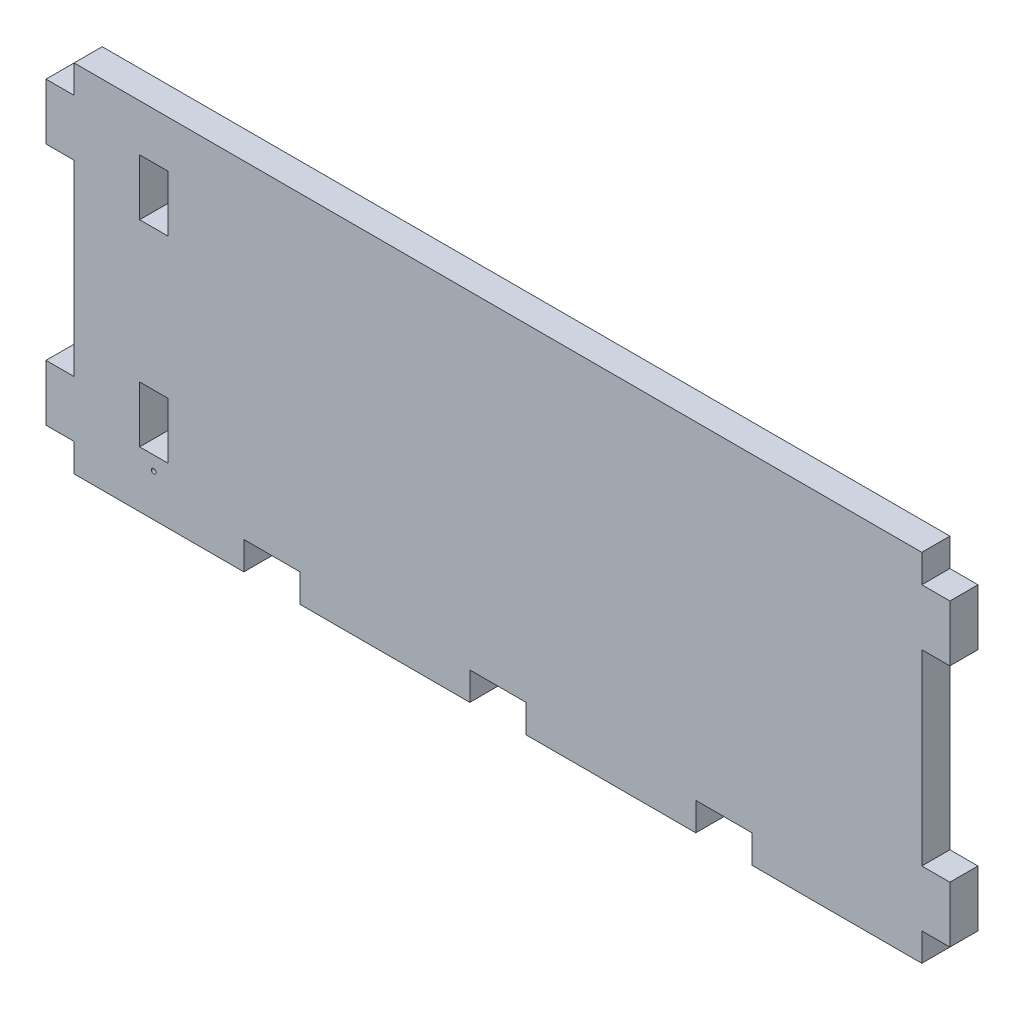
SolidWorks part; units mm, degrees
ref_plane "Front Plane" through (0, 0, 0) normal (0, 0, 1) x (1, 0, 0)
ref_plane "Top Plane" through (0, 0, 0) normal (0, 1, 0) x (1, 0, 0)
ref_plane "Right Plane" through (0, 0, 0) normal (1, 0, 0) x (0, 0, -1)
sketch "Sketch2" plane through (0, 0, 0) normal (0, 1, 0) x (1, 0, 0)
  line L0 (0, 0) -> (0, 6) construction
  dimension "D1" = 6
sketch "Sketch1" plane through (0, 0, 0) normal (0, 0, 1) x (1, 0, 0)
  line L0 (-90.5, 32) -> (-90.5, 38)
  line L1 (-96.5, -38) -> (96.5, -38)
  line L2 (-96.5, -38) -> (-96.5, 38)
  line L3 (-96.5, 38) -> (96.5, 38)
  line L4 (96.5, -38) -> (96.5, 38)
  line L5 (-96.5, -38) -> (96.5, 38) construction
  line L6 (-96.5, 38) -> (96.5, -38) construction
  line L7 (-96.5, -32) -> (-90.5, -32)
  line L8 (-96.5, -32) -> (-96.5, -20)
  line L9 (-96.5, -20) -> (-90.5, -20)
  line L10 (-90.5, -32) -> (-90.5, -20)
  line L11 (-96.5, 32) -> (-90.5, 32)
  line L12 (-96.5, 32) -> (-96.5, 20)
  line L13 (-96.5, 20) -> (-90.5, 20)
  line L14 (-90.5, 32) -> (-90.5, 20)
  line L15 (96.5, 32) -> (90.5, 32)
  line L16 (96.5, 32) -> (96.5, 20)
  line L17 (96.5, 20) -> (90.5, 20)
  line L18 (90.5, 32) -> (90.5, 20)
  line L19 (90.5, -20) -> (96.5, -20)
  line L20 (90.5, -20) -> (90.5, -32)
  line L21 (90.5, -32) -> (96.5, -32)
  line L22 (96.5, -20) -> (96.5, -32)
  line L23 (-90.5, -32) -> (-90.5, -38)
  line L24 (-90.5, 20) -> (-90.5, -20)
  line L25 (90.5, 32) -> (90.5, 38)
  line L26 (90.5, 20) -> (90.5, -20)
  line L27 (90.5, -32) -> (90.5, -38)
  line L28 (-90.5, 0) -> (-76.5, 0) construction
  line L29 (54.25, -32) -> (90.5, -32) construction
  line L30 (-76.5, 0) -> (-76.5, 16) construction
  line L31 (-76.5, 16) -> (-76.5, 28)
  line L32 (-76.5, 28) -> (-76.5, 38) construction
  line L33 (-76.5, 28) -> (-70.5, 28)
  line L34 (-70.5, 28) -> (-70.5, 16)
  line L35 (-70.5, 16) -> (-76.5, 16)
  line L36 (-76.5, -26) -> (-76.5, -14)
  line L37 (-76.5, -14) -> (-70.5, -14)
  line L38 (-70.5, -14) -> (-70.5, -26)
  line L39 (-70.5, -26) -> (-76.5, -26)
  line L40 (-76.5, -32) -> (-76.5, -26) construction
  line L41 (-76.5, -14) -> (-76.5, 0) construction
  line L42 (-90.5, -32) -> (-54.25, -32) construction
  line L43 (6, -38) -> (-6, -38)
  line L44 (6, -38) -> (6, -32)
  line L45 (6, -32) -> (-6, -32)
  line L46 (-6, -38) -> (-6, -32)
  line L47 (42.25, -38) -> (54.25, -38)
  line L48 (42.25, -38) -> (42.25, -32)
  line L49 (42.25, -32) -> (54.25, -32)
  line L50 (54.25, -38) -> (54.25, -32)
  line L51 (-42.25, -38) -> (-54.25, -38)
  line L52 (-42.25, -38) -> (-42.25, -32)
  line L53 (-42.25, -32) -> (-54.25, -32)
  line L54 (-54.25, -38) -> (-54.25, -32)
  line L55 (-42.25, -32) -> (-6, -32) construction
  line L56 (6, -32) -> (42.25, -32) construction
  point P0 (0, 0)
  dimension "D1" = 193
  dimension "D2" = 76
  dimension "D3" = 6
  dimension "D4" = 12
  dimension "D5" = 14
  dimension "D6" = 10
extrude "Boss-Extrude1" add sketch "Sketch1" against normal up to vertex (6 mm away) contours L1 L54 L53 L52 L46 L45 L44 L48 L49 L50 L27 L20 L26 L18 L25 L3 L0 L14 L24 L10 L23 L34 L35 L31 L33 L38 L39 L36 L37 | L7 L10 L9 L2 | L14 L11 L2 L13 | L15 L18 L17 L4 | L20 L21 L4 L19 region at (-93.5, 26, 0) region at (0.7901, 0.5536, 0) region at (-93.5, -26, 0) region at (93.5, 26, 0) region at (93.5, -26, 0) up to point (0, 0, -6)
sketch "Sketch3" plane through (0, 0, 0) normal (0, 0, 1) x (1, 0, 0)
  line L0 (-73.5, -26) -> (-73.5, -29) construction
  line L1 (-70.5, -26) -> (-76.5, -26) construction
  line L2 (-90.5, -38) -> (-54.25, -38) construction
  circle A0 centre (-73.5, -29) radius 0.5
  dimension "D2" = 1
  dimension "D1" = 9
extrude "Cut-Extrude1" cut sketch "Sketch3" against normal through all
equation "\"t_wood\"= 6' Thickness of the wood"
equation "\"t_glass\"= 2.5'Thickness of glass panels"
equation "\"w_glass\"= 181"
equation "\"h_glass\"= 151"
equation "\"h_food_internal\" = 60"
equation "\"entry_height\"= 20"
equation "\"entry diameter\"= 8"
equation "\"glass_bottom_overlap\"= 8"
equation "\"default_finger_size\"= 12"
equation "\"brood_depth\"= 42"
equation "\"outer_box_depth\" = \"brood_depth\" + ( 2 * \"t_glass\" ) + ( 2 * \"t_wood\" )"
equation "\"outer_box_width\"= \"w_glass\" + ( 2 * \"t_wood\" )"
equation "\"food_top_clearance\"= 10"
equation "\"outer_box_height\"= \"t_wood\" + \"h_glass\" + \"t_wood\" + \"h_food_internal\" + \"food_top_clearance\" + \"t_wood\""
equation "\"food_internal_depth\"= \"brood_depth\" + \"t_glass\" + \"t_glass\" - \"t_wood\" - \"t_wood\""
equation "\"food_channel_clearance_width\"= 14"
equation "\"bar_top_play\"= 0.5"
equation "\"bar_entry_angle\"= 10"
equation "\"bar_width\"= 20"
equation "\"entry_disk_play\"= 0.3"
equation "\"D1@Sketch2\"=\"t_wood\""
equation "\"D1@Sketch1\"=\"outer_box_width\""
equation "\"D2@Sketch1\"=\"h_food_internal\"+\"t_wood\"+\"food_top_clearance\""
equation "\"D3@Sketch1\"=\"t_wood\""
equation "\"D4@Sketch1\"=\"default_finger_size\""
equation "\"D5@Sketch1\"=\"food_channel_clearance_width\""
equation "\"D6@Sketch1\"=\"food_top_clearance\""
